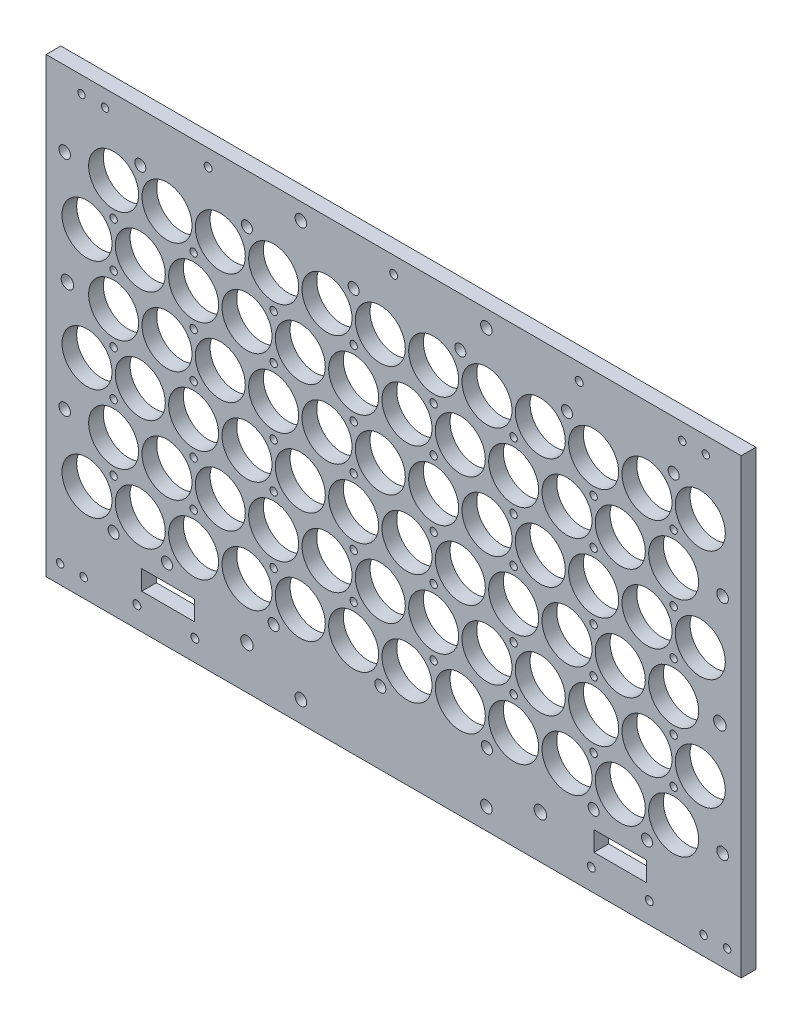
SolidWorks part; units mm, degrees
material "ABS"
ref_plane "X-Y Datum" through (0, 0, 0) normal (0, 0, 1) x (1, 0, 0)
ref_plane "X-Z Datum" through (0, 0, 0) normal (0, 1, 0) x (1, 0, 0)
ref_plane "Y-Z Datum" through (0, 0, 0) normal (1, 0, 0) x (0, 0, -1)
sketch "Sketch1" plane through (0, 0, 0) normal (0, 0, 1) x (1, 0, 0)
  line L1 (-143.025, 70.775) -> (143.025, 70.775)
  line L2 (-143.025, 70.775) -> (-143.025, -70.775)
  line L3 (-143.025, -70.775) -> (143.025, -70.775)
  line L4 (143.025, 70.775) -> (143.025, -70.775)
  line L5 (-143.025, 70.775) -> (143.025, -70.775) construction
  line L6 (-143.025, -70.775) -> (143.025, 70.775) construction
  line L13 (-149.85, -102.6) -> (149.85, -102.6)
  line L14 (-149.85, 91.65) -> (149.85, 91.65)
  line L15 (-149.85, 91.65) -> (-149.85, -102.6)
  line L16 (149.85, 91.65) -> (149.85, -102.6)
  line L17 (149.85, 70.775) -> (149.85, -70.775) construction
  line L18 (-143.025, 91.65) -> (143.025, 91.65) construction
  line L19 (-143.025, -102.6) -> (143.025, -102.6) construction
  line L20 (-149.85, 70.775) -> (-149.85, -70.775) construction
  line L21 (-132.25, -60) -> (-109.25, -60) construction
  circle A0 centre (-132.25, -60) radius 10.775
  circle A1 centre (-109.25, -60) radius 10.775 construction
  circle A2 centre (-120.75, -36) radius 10.775
  point P0 (0, 0)
  point P16 (-120.75, -60)
  dimension "D1" = 21.55
  dimension "D2" = 23
  dimension "D3" = 24
  dimension "D5" = 141.55
  dimension "D6" = 286.05
  dimension "D7" = 31.825
  dimension "D8" = 20.875
  dimension "D9" = 6.825
  dimension "D10" = 6.825
extrude "Boss-Extrude1" add sketch "Sketch1" along normal blind 6.35 contours A0 L3 L4 L1 L2 A2 | A2 | A0 | A0 L2 L3 | L1 L4 L3 L2 region at (2.4105, 0.9241, 0) region at (-140.6182, -68.3682, 0) region at (-132.25, -60, 0) region at (-146.2785, -5.475, 0) region at (-120.75, -36, 0)
sketch "Sketch3" plane through (0, 0, 6.35) normal (0, 0, 1) x (1, 0, 0)
  line L4 (143.025, 70.775) -> (-143.025, 70.775)
  line L5 (143.025, -70.775) -> (143.025, 70.775)
  line L6 (-143.025, -70.775) -> (143.025, -70.775)
  line L7 (-143.025, 70.775) -> (-143.025, -70.775)
  line L8 (143.025, 70.775) -> (-143.025, 70.775)
  line L9 (143.025, -70.775) -> (143.025, 70.775)
  line L10 (-143.025, -70.775) -> (143.025, -70.775)
  line L11 (-143.025, 70.775) -> (-143.025, -70.775)
  circle A1 centre (-120.75, -36) radius 10.775
  circle A2 centre (-120.75, -36) radius 10.775
  circle A3 centre (-132.25, -60) radius 10.775
  circle A4 centre (-132.25, -60) radius 10.775
  dimension "D1" = 0
  dimension "D2" = 0
  dimension "D3" = 0
extrude "Cut-Extrude1" cut sketch "Sketch3" against normal through all contours A4 region at (-132.25, -60, 6.35)
sketch "Sketch4" plane through (0, 0, 6.35) normal (0, 0, 1) x (1, 0, 0)
  line L4 (143.025, 70.775) -> (-143.025, 70.775)
  line L5 (143.025, -70.775) -> (143.025, 70.775)
  line L6 (-143.025, -70.775) -> (143.025, -70.775)
  line L7 (-143.025, 70.775) -> (-143.025, -70.775)
  line L8 (143.025, 70.775) -> (-143.025, 70.775)
  line L9 (143.025, -70.775) -> (143.025, 70.775)
  line L10 (-143.025, -70.775) -> (143.025, -70.775)
  line L11 (-143.025, 70.775) -> (-143.025, -70.775)
  circle A1 centre (-120.75, -36) radius 10.775
  circle A2 centre (-120.75, -36) radius 10.775
  circle A3 centre (-132.25, -60) radius 10.775
  circle A4 centre (-132.25, -60) radius 10.775
  dimension "D1" = 0
  dimension "D2" = 0
  dimension "D3" = 0
extrude "Cut-Extrude2" cut sketch "Sketch4" against normal through all contours A2 region at (-120.75, -36, 6.35)
pattern_linear "LPattern1" count 12 spacing 23 along (1, 0, 0) of "Cut-Extrude1", "Cut-Extrude2"
pattern_linear "LPattern2" count 3 spacing 48 along (0, 1, 0) of "LPattern1"
sketch "Sketch5" plane through (0, 0, 6.35) normal (0, 0, 1) x (1, 0, 0)
  line L4 (105.3154, -79.3475) -> (90.1846, -79.3475)
  line L5 (90.37, -80.3) -> (90.37, -83.4115)
  line L6 (90.37, -83.4115) -> (105.13, -83.4115)
  line L7 (105.13, -83.4115) -> (105.13, -80.3)
  line L8 (105.3154, -79.3475) -> (90.1846, -79.3475)
  line L9 (90.37, -80.3) -> (90.37, -83.4115)
  line L10 (90.37, -83.4115) -> (105.13, -83.4115)
  line L11 (105.13, -83.4115) -> (105.13, -80.3)
  line L12 (-108.668, -78.95) -> (-108.668, -87.4115)
  line L13 (-108.668, -87.4115) -> (-85.908, -87.4115)
  line L14 (-85.908, -87.4115) -> (-85.908, -78.95)
  line L15 (86.37, -78.95) -> (86.37, -87.4115)
  line L16 (-89.7226, -79.3475) -> (-104.8534, -79.3475)
  line L17 (-104.668, -80.3) -> (-104.668, -83.4115)
  line L18 (-104.668, -83.4115) -> (-89.908, -83.4115)
  line L19 (-89.908, -83.4115) -> (-89.908, -80.3)
  line L20 (-89.7226, -79.3475) -> (-104.8534, -79.3475)
  line L21 (-104.668, -80.3) -> (-104.668, -83.4115)
  line L22 (-104.668, -83.4115) -> (-89.908, -83.4115)
  line L23 (-89.908, -83.4115) -> (-89.908, -80.3)
  line L24 (86.37, -87.4115) -> (109.13, -87.4115)
  line L25 (109.13, -87.4115) -> (109.13, -78.95)
  line L26 (149.85, -78.95) -> (-149.85, -78.95) construction
  line L27 (149.85, -78.95) -> (-149.85, -78.95)
  line L28 (109.13, -87.4115) -> (109.13, -80.3) construction
  line L29 (86.37, -80.3) -> (86.37, -87.4115) construction
  line L30 (-85.908, -87.4115) -> (-85.908, -80.3) construction
  line L31 (-108.668, -80.3) -> (-108.668, -87.4115) construction
  arc A2 (90.37, -80.3) -> (90.1846, -79.3475) centre (87.83, -80.3) ccw
  arc A3 (105.3154, -79.3475) -> (105.13, -80.3) centre (107.67, -80.3) ccw
  arc A4 (90.37, -80.3) -> (90.1846, -79.3475) centre (87.83, -80.3) ccw
  arc A5 (105.3154, -79.3475) -> (105.13, -80.3) centre (107.67, -80.3) ccw
  arc A8 (-104.668, -80.3) -> (-104.8534, -79.3475) centre (-107.208, -80.3) ccw
  arc A9 (-89.7226, -79.3475) -> (-89.908, -80.3) centre (-87.368, -80.3) ccw
  arc A10 (-104.668, -80.3) -> (-104.8534, -79.3475) centre (-107.208, -80.3) ccw
  arc A11 (-89.7226, -79.3475) -> (-89.908, -80.3) centre (-87.368, -80.3) ccw
  dimension "D1" = 0
  dimension "D2" = 0
  dimension "D3" = 4
extrude "Cut-Extrude3" cut sketch "Sketch5" against normal through all contours L25 L27 L15 L24 L8 A5 L11 L10 L9 A4 | A5 L8 A4 L9 L10 L11 | L14 L27 L12 L13 L20 A11 L23 L22 L21 A10 | A11 L20 A10 L21 L22 L23 region at (97.75, -81.376, 6.35) region at (-97.288, -83.9995, 6.35) region at (97.75, -83.9995, 6.35) region at (-97.288, -81.376, 6.35)
sketch "Sketch7" plane through (0, 0, 6.35) normal (0, 0, 1) x (1, 0, 0)
  point P0 (0, 85.3)
  point P1 (80, 85.3)
  point P3 (-124.45, 85.3)
  point P5 (-134.61, 85.3)
  point P7 (-133.6575, -94.6)
  point P9 (-143.8175, -94.6)
  point P11 (133.6575, -94.6)
  point P13 (143.8175, -94.6)
  point P17 (124.45, 85.3)
  point P19 (134.61, 85.3)
  point P21 (110.25, -93.5057)
  point P23 (85.25, -93.5057)
  point P28 (-80, 85.3)
hole_wizard "M3 Clearance Hole1" positions "Sketch8" profile "Sketch9" hole size "M3" standard "ANSI Metric" end condition through all
sketch "Sketch8" plane through (0, 0, 6.35) normal (0, 0, 1) x (1, 0, 0)
  point P3 (124.45, 85.3)
  point P6 (134.61, 85.3)
  point P12 (-124.45, 85.3)
  point P15 (-134.61, 85.3)
  point P18 (-143.8175, -94.6)
  point P21 (-133.6575, -94.6)
  point P24 (133.6575, -94.6)
  point P27 (143.8175, -94.6)
sketch "Sketch9" plane through (124.45, 85.3, 6.35) normal (1, 0, 0) x (0, -1, 0)
  line L0 (0, 0) -> (0, 6.35)
  line L1 (0, 6.35) -> (1.6, 6.35)
  line L2 (1.6, 6.35) -> (1.6, 0)
  line L5 (1.6, 0) -> (0, 0)
  line L11 (0, -6.35) -> (0, 107.95) construction
  dimension "Thru Hole Dia." = 3.2
  dimension "Thru Hole Depth" = 6.35
hole_wizard "M3 Clearance Hole2" positions "Sketch20" profile "Sketch13" hole size "M3" standard "ANSI Metric" end condition through all
sketch "Sketch20" plane through (0, 0, 6.35) normal (0, 0, 1) x (1, 0, 0)
  point P0 (110.25, -93.5057)
  point P3 (85.25, -93.5057)
  point P6 (-80, 85.3)
  point P9 (0, 85.3)
  point P12 (80, 85.3)
sketch "Sketch13" plane through (110.25, -93.5057, 6.35) normal (1, 0, 0) x (0, -1, 0)
  line L0 (0, 0) -> (0, 6.35)
  line L1 (0, 6.35) -> (1.7, 6.35)
  line L2 (1.7, 6.35) -> (1.7, 0)
  line L5 (1.7, 0) -> (0, 0)
  line L11 (0, -6.35) -> (0, 107.95) construction
  dimension "Thru Hole Dia." = 3.4
  dimension "Thru Hole Depth" = 6.35
sketch "Sketch14" plane through (0, 0, 6.35) normal (0, 0, 1) x (1, 0, 0)
  line L0 (131.525, -12) -> (149.85, -12) construction
  line L1 (149.85, 91.65) -> (149.85, -102.6) construction
  line L2 (-131.525, 12) -> (-149.85, 12) construction
  line L3 (-149.85, 91.65) -> (-149.85, -102.6) construction
  line L4 (149.85, -78.95) -> (-149.85, -78.95) construction
  line L5 (149.85, -78.95) -> (-149.85, -78.95) construction
  line L6 (149.85, -83.95) -> (-149.85, -83.95) construction
  line L7 (68.55, -70.9014) -> (57.95, -70.9014) construction
  line L8 (68.55, -67.0427) -> (68.55, -74.76) construction
  line L9 (57.95, -67.0427) -> (57.95, -74.76) construction
  line L10 (63.25, -70.9014) -> (63.25, -83.95) construction
  line L18 (0, -3.4925) -> (0, 3.4925) construction
  circle A0 centre (120.75, -12) radius 10.775 construction
  circle A1 centre (-120.75, 12) radius 10.775 construction
  circle A2 centre (140.6875, -12) radius 2.7
  circle A3 centre (-140.6875, 12) radius 2.7
  circle A4 centre (63.25, -83.95) radius 2.7
  circle A6 centre (-63.25, -83.95) radius 2.7
  circle A8 centre (0, -83.95) radius 2.7
  dimension "D1" = 5.4
  dimension "D3" = 5.4
  dimension "D2" = 5
extrude "Cut-Extrude4" cut sketch "Sketch14" against normal through all contours A6 | A4 | A3 | A2 region at (-140.6875, 12, 6.35) region at (63.25, -83.95, 6.35) region at (-63.25, -83.95, 6.35)
sketch "Sketch15" plane through (0, 0, 6.35) normal (0, 0, 1) x (1, 0, 0)
  line L0 (-6.35, 85.3) -> (86.35, 85.3) construction
  line L1 (-6.35, 90.65) -> (-6.35, 79.95) construction
  line L2 (86.35, 79.95) -> (86.35, 90.65) construction
  line L3 (-86.35, 85.3) -> (6.35, 85.3) construction
  line L4 (-86.35, 90.65) -> (-86.35, 79.95) construction
  line L5 (6.35, 79.95) -> (6.35, 90.65) construction
  line L6 (131.525, 36) -> (149.85, 36) construction
  line L7 (149.85, 94.825) -> (149.85, -105.775) construction
  line L8 (131.525, -60) -> (149.85, -60) construction
  line L9 (-131.525, -36) -> (-149.85, -36) construction
  line L10 (-149.85, -105.775) -> (-149.85, 94.825) construction
  line L11 (-131.525, 60) -> (-149.85, 60) construction
  line L12 (-40, 85.3) -> (-40, -102.6) construction
  line L13 (-149.85, -102.6) -> (149.85, -102.6) construction
  line L14 (40, 85.3) -> (40, -102.6) construction
  line L16 (85.25, -93.5057) -> (-85.25, -93.5057) construction
  circle A0 centre (-40, 85.3) radius 2.5
  circle A1 centre (40, 85.3) radius 2.5
  circle A2 centre (120.75, 36) radius 10.775 construction
  circle A3 centre (120.75, -60) radius 10.775 construction
  circle A4 centre (141.85, 36) radius 2.5
  circle A5 centre (141.85, -60) radius 2.5
  circle A6 centre (-120.75, -36) radius 10.775 construction
  circle A7 centre (-120.75, 60) radius 10.775 construction
  circle A8 centre (-141.85, -36) radius 2.5
  circle A9 centre (-141.85, 60) radius 2.5
  circle A10 centre (-40, -93.5057) radius 2.5
  circle A11 centre (40, -93.5057) radius 2.5
  dimension "D1" = 5
  dimension "D2" = 8
  dimension "D3" = 8
  dimension "D4" = 8
  dimension "D5" = 8
extrude "Cut-Extrude5" cut sketch "Sketch15" against normal through all
sketch "Sketch18" plane through (0, 0, 6.35) normal (0, 0, 1) x (1, 0, 0)
  circle A0 centre (-120.75, -71.41) radius 1.5875 construction
  circle A1 centre (-97.75, -71.41) radius 1.5875 construction
  circle A2 centre (-51.75, -71.41) radius 1.5875 construction
  circle A3 centre (-5.75, -71.41) radius 1.5875 construction
  circle A4 centre (40.25, -71.41) radius 1.5875 construction
  circle A5 centre (-109.25, 71.41) radius 1.5875 construction
  circle A6 centre (-63.25, 71.41) radius 1.5875 construction
  circle A7 centre (-17.25, 71.41) radius 1.5875 construction
  circle A8 centre (28.75, 71.41) radius 1.5875 construction
  circle A9 centre (74.75, 71.41) radius 1.5875 construction
  circle A10 centre (120.75, 71.41) radius 1.5875 construction
  circle A11 centre (86.25, -71.41) radius 1.5875 construction
  circle A12 centre (109.25, -71.41) radius 1.5875 construction
  circle A13 centre (-120.75, -71.41) radius 1.5875 construction
  circle A14 centre (-97.75, -71.41) radius 1.5875 construction
  circle A15 centre (-51.75, -71.41) radius 1.5875 construction
  circle A16 centre (-5.75, -71.41) radius 1.5875 construction
  circle A17 centre (40.25, -71.41) radius 1.5875 construction
  circle A18 centre (-109.25, 71.41) radius 1.5875 construction
  circle A19 centre (-63.25, 71.41) radius 1.5875 construction
  circle A20 centre (-17.25, 71.41) radius 1.5875 construction
  circle A21 centre (28.75, 71.41) radius 1.5875 construction
  circle A22 centre (74.75, 71.41) radius 1.5875 construction
  circle A23 centre (120.75, 71.41) radius 1.5875 construction
  circle A24 centre (86.25, -71.41) radius 1.5875 construction
  circle A25 centre (109.25, -71.41) radius 1.5875 construction
  circle A26 centre (109.25, -71.41) radius 2.3813
  circle A27 centre (86.25, -71.41) radius 2.3813
  circle A28 centre (120.75, 71.41) radius 2.3813
  circle A29 centre (74.75, 71.41) radius 2.3813
  circle A30 centre (28.75, 71.41) radius 2.3813
  circle A31 centre (-17.25, 71.41) radius 2.3812
  circle A32 centre (-63.25, 71.41) radius 2.3812
  circle A33 centre (-109.25, 71.41) radius 2.3813
  circle A34 centre (40.25, -71.41) radius 2.3812
  circle A35 centre (-5.75, -71.41) radius 2.3812
  circle A36 centre (-51.75, -71.41) radius 2.3812
  circle A37 centre (-97.75, -71.41) radius 2.3813
  circle A38 centre (-120.75, -71.41) radius 2.3813
  dimension "D1" = 4.7625
extrude "Cut-Extrude7" cut sketch "Sketch18" against normal through all
sketch "Sketch19" plane through (0, 91.65, 0) normal (0, 1, 0) x (1, 0, 0)
  line L4 (149.85, 0) -> (-149.85, 0)
  line L5 (-149.85, 0) -> (-149.85, -6.35)
  line L6 (-149.85, -6.35) -> (149.85, -6.35)
  line L7 (149.85, -6.35) -> (149.85, 0)
  line L8 (149.85, 0) -> (-149.85, 0)
  line L9 (-149.85, 0) -> (-149.85, -6.35)
  line L10 (-149.85, -6.35) -> (149.85, -6.35)
  line L11 (149.85, -6.35) -> (149.85, 0)
  dimension "D1" = 0
extrude "Boss-Extrude2" add sketch "Sketch19" along normal blind 0.7937
sketch "Sketch22" plane through (0, 0, 6.35) normal (0, 0, 1) x (1, 0, 0)
  line L0 (132.25, -36) -> (120.75, -60) construction
  line L1 (120.75, -60) -> (109.25, -36) construction
  line L2 (109.25, -36) -> (132.25, -36) construction
  line L3 (120.75, -36) -> (120.75, -60) construction
  line L4 (127.5939, -45.7171) -> (113.9061, -45.7171) construction
  line L5 (109.25, -36) -> (97.75, -60) construction
  line L6 (97.75, -60) -> (86.25, -36) construction
  line L7 (86.25, -36) -> (109.25, -36) construction
  line L8 (97.75, -60) -> (97.75, -36) construction
  line L9 (113.9061, -45.7171) -> (90.9061, -45.7171) construction
  line L10 (86.25, -36) -> (74.75, -60) construction
  line L11 (74.75, -60) -> (63.25, -36) construction
  line L12 (63.25, -36) -> (86.25, -36) construction
  line L13 (74.75, -36) -> (74.75, -60) construction
  line L14 (90.9061, -45.7171) -> (67.9061, -45.7171) construction
  line L15 (74.75, -60) -> (97.75, -60) construction
  line L16 (86.25, -36) -> (86.25, -60) construction
  line L17 (79.4061, -50.2829) -> (93.0939, -50.2829) construction
  circle A0 centre (132.25, -36) radius 10.775 construction
  circle A1 centre (109.25, -36) radius 10.775 construction
  circle A2 centre (120.75, -45.7171) radius 1.5875
  circle A3 centre (86.25, -36) radius 10.775 construction
  circle A6 centre (74.75, -60) radius 10.775 construction
  circle A7 centre (97.75, -60) radius 10.775 construction
  circle A8 centre (86.25, -50.2829) radius 1.5875
  dimension "D1" = 3.175
extrude "Cut-Extrude8" cut sketch "Sketch22" against normal through all
pattern_linear "LPattern3" count 3 spacing 48 along (0, 1, 0) of "Cut-Extrude8"
sketch "Sketch23" plane through (0, 0, 6.35) normal (0, 0, 1) x (1, 0, 0)
  line L0 (132.25, -36) -> (120.75, -12) construction
  line L1 (120.75, -12) -> (109.25, -36) construction
  line L2 (109.25, -36) -> (132.25, -36) construction
  line L3 (120.75, -36) -> (120.75, -12) construction
  line L4 (109.25, -36) -> (97.75, -12) construction
  line L5 (97.75, -12) -> (86.25, -36) construction
  line L6 (86.25, -36) -> (109.25, -36) construction
  line L7 (97.75, -36) -> (97.75, -12) construction
  line L8 (127.5939, -26.2829) -> (90.9061, -26.2829) construction
  line L9 (86.25, -36) -> (63.25, -36) construction
  line L10 (63.25, -36) -> (74.75, -12) construction
  line L11 (74.75, -12) -> (86.25, -36) construction
  line L12 (74.75, -36) -> (74.75, -12) construction
  line L13 (90.9061, -26.2829) -> (67.9061, -26.2829) construction
  line L14 (74.75, -12) -> (97.75, -12)
  line L15 (86.25, -12) -> (86.25, -36) construction
  line L16 (79.4061, -21.7171) -> (93.0939, -21.7171) construction
  circle A0 centre (132.25, -36) radius 10.775 construction
  circle A1 centre (86.25, -36) radius 10.775 construction
  circle A2 centre (120.75, -26.2829) radius 1.5875
  circle A5 centre (74.75, -12) radius 10.775 construction
  circle A6 centre (97.75, -12) radius 10.775 construction
  circle A7 centre (86.25, -21.7171) radius 1.5875
  dimension "D1" = 3.175
extrude "Cut-Extrude9" cut sketch "Sketch23" against normal through all contours A7 | A2 region at (120.75, -26.2829, 6.35) region at (86.25, -21.7171, 6.35)
pattern_linear "LPattern4" count 2 spacing 48 along (0, 1, 0) of "Cut-Extrude9"
pattern_linear "LPattern5" count 4 spacing 69 along (-1, 0, 0) of "Cut-Extrude8", "LPattern3", "Cut-Extrude9", "LPattern4"
sketch "Sketch25" plane through (0, 0, 6.35) normal (0, 0, 1) x (1, 0, 0)
  line L0 (-85.712, -93.486) -> (-110.712, -93.486)
  line L1 (-149.85, -102.6) -> (149.85, -102.6) construction
  line L3 (-149.85, 92.4437) -> (-149.85, -102.6) construction
  circle A0 centre (-110.712, -93.486) radius 1.5
  circle A1 centre (-85.712, -93.486) radius 1.5
  point P7 (-98.212, -93.486)
  dimension "D1" = 3
  dimension "D2" = 25
  dimension "D3" = 9.114
  dimension "D4" = 39.138
hole_wizard "M3 Clearance Hole3" positions "Sketch30" profile "Sketch29" hole size "M3" standard "ANSI Metric" end condition through all
sketch "Sketch30" plane through (0, 0, 6.35) normal (0, 0, 1) x (1, 0, 0)
  point P0 (-85.712, -93.486)
  point P3 (-110.712, -93.486)
sketch "Sketch29" plane through (-85.712, -93.486, 6.35) normal (1, 0, 0) x (0, -1, 0)
  line L0 (0, 0) -> (0, 6.35)
  line L1 (0, 6.35) -> (1.7, 6.35)
  line L2 (1.7, 6.35) -> (1.7, 0)
  line L5 (1.7, 0) -> (0, 0)
  line L11 (0, -6.35) -> (0, 107.95) construction
  dimension "Thru Hole Dia." = 3.4
  dimension "Thru Hole Depth" = 6.35
